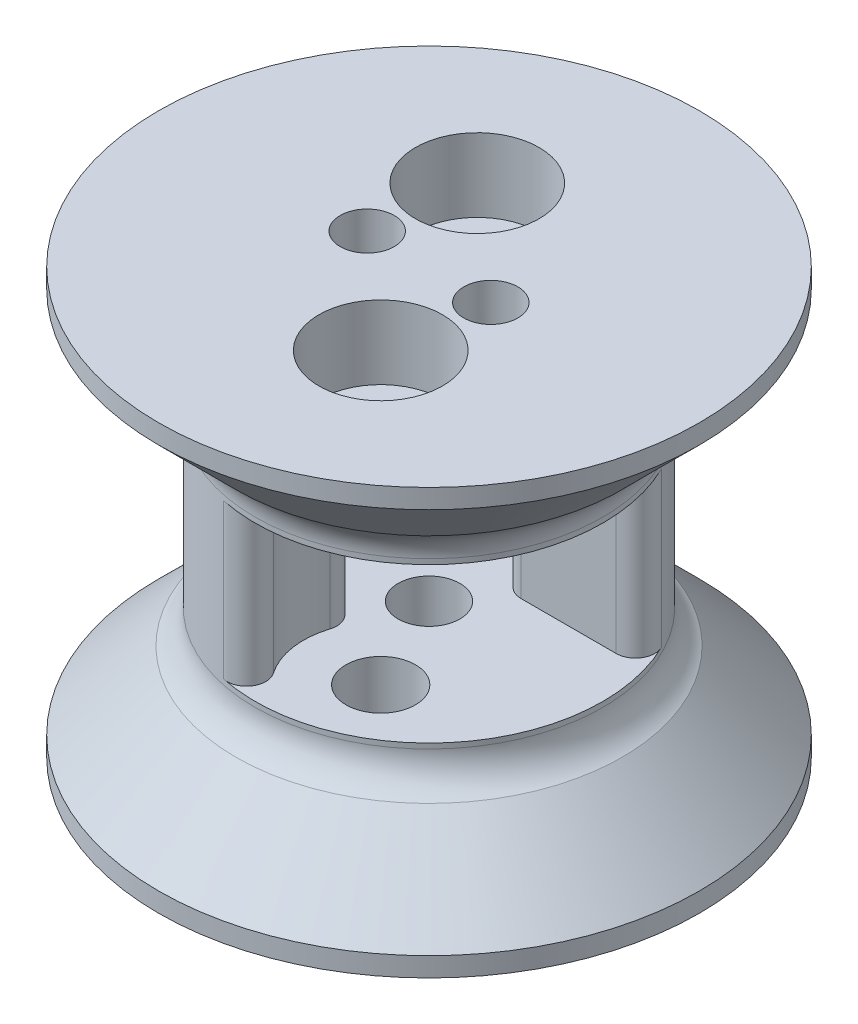
SolidWorks part; units mm, degrees
ref_plane "Front Plane" through (0, 0, 0) normal (0, 0, 1) x (1, 0, 0)
ref_plane "Top Plane" through (0, 0, 0) normal (0, 1, 0) x (1, 0, 0)
ref_plane "Right Plane" through (0, 0, 0) normal (1, 0, 0) x (0, 0, -1)
sketch "Sketch1" plane through (0, 0, 0) normal (0, 1, 0) x (1, 0, 0)
  circle A0 centre (0, 0) radius 11.43
  dimension "D1" = 22.86
extrude "Boss-Extrude1" add sketch "Sketch1" along normal mid plane 27.94
sketch "Sketch2" plane through (0, 0, 0) normal (0, 1, 0) x (1, 0, 0)
  line L0 (-11.43, 0) -> (11.43, 0) construction
  line L1 (0.7906, 3.175) -> (10.9802, 3.175)
  line L2 (-0.7906, -3.175) -> (-10.9802, -3.175)
  arc A0 (0.7906, 3.175) -> (-1.9084, 11.2696) centre (-3.175, 6.35) ccw
  circle A1 centre (0, 0) radius 11.43 construction
  circle A2 centre (-3.175, 6.35) radius 4.7625 construction
  circle A6 centre (0, 0) radius 11.43
  arc A7 (-0.7906, -3.175) -> (1.9084, -11.2696) centre (3.175, -6.35) ccw
  point P9 (0, 0)
  point P10 (0, 0)
  point P18 (0, 0)
  point P19 (0, 0)
  point P20 (-5.08, 2.54)
  point P21 (0, 0)
  point P22 (0, 0)
  point P23 (0, 0)
  point P24 (0, 0)
  dimension "D1" = 10.16
  dimension "D5" = 9.525
  dimension "D4" = 3.175
  dimension "D2" = 6.35
  dimension "D3" = 6.35
  dimension "D6" = 2
extrude "Cut-Extrude1" cut sketch "Sketch2" against normal mid plane 10.16 contours L2 A7 A6 L1 A0 region at (0, 0, 0)
sketch "Sketch3" plane through (0, 0, 0) normal (0, 1, 0) x (1, 0, 0)
  circle A0 centre (-3.175, 6.35) radius 2.286
  circle A1 centre (3.175, -6.35) radius 2.286
  dimension "D1" = 4.572
  dimension "D2" = 4.572
extrude "Cut-Extrude2" cut sketch "Sketch3" against normal through all both and the other way through all
fillet "Fillet1" radius 1.27 6 edges at (-0.7906, 0, 3.175) (0.7906, 0, -3.175) (-1.9084, 0, -11.2696) (1.9084, 0, 11.2696) (-10.9802, 0, 3.175) (10.9802, 0, -3.175)
sketch "Sketch4" plane through (0, 13.97, 0) normal (0, 1, 0) x (1, 0, 0)
  circle A0 centre (0, 0) radius 11.43
  circle A1 centre (0, 0) radius 17.78
  circle A2 centre (0, 0) radius 11.43 construction
  dimension "D1" = 6.35
extrude "Boss-Extrude2" add sketch "Sketch4" against normal blind 6.35
mirror "Mirror1" about plane through (0, 0, 0) normal (0, 1, 0) of "Boss-Extrude2"
sketch "Sketch5" plane through (0, 13.97, 0) normal (0, 1, 0) x (1, 0, 0)
  circle A0 centre (-3.175, 6.35) radius 4.064
  circle A1 centre (3.175, -6.35) radius 4.064
  dimension "D1" = 8.128
extrude "Cut-Extrude3" cut sketch "Sketch5" against normal blind 4.826 and the other way through all
sketch "Sketch7" plane through (0, 0, 0) normal (0, 1, 0) x (1, 0, 0)
  line L0 (0, 0) -> (0, 17.78) construction
  circle A0 centre (-4.064, 0) radius 1.778
  circle A2 centre (0, 0) radius 17.78 construction
  circle A3 centre (4.064, 0) radius 1.778
  point P10 (0, 0)
  dimension "D2" = 3.556
  dimension "D1" = 4.064
extrude "Cut-Extrude4" cut sketch "Sketch7" along normal through all
chamfer "Chamfer1" distance 5.08 angle 45 2 edges at (0, -7.62, 17.78) (0, 7.62, 17.78)
fillet "Fillet2" radius 2.54 2 edges at (0, 7.62, 11.43) (0, -7.62, -11.43)
sketch "Sketch9" plane through (0, -13.97, 0) normal (0, -1, 0) x (1, 0, 0)
  circle A0 centre (0, 0) radius 2.032
  dimension "D1" = 4.064
extrude "Cut-Extrude5" cut sketch "Sketch9" against normal blind 10.16
